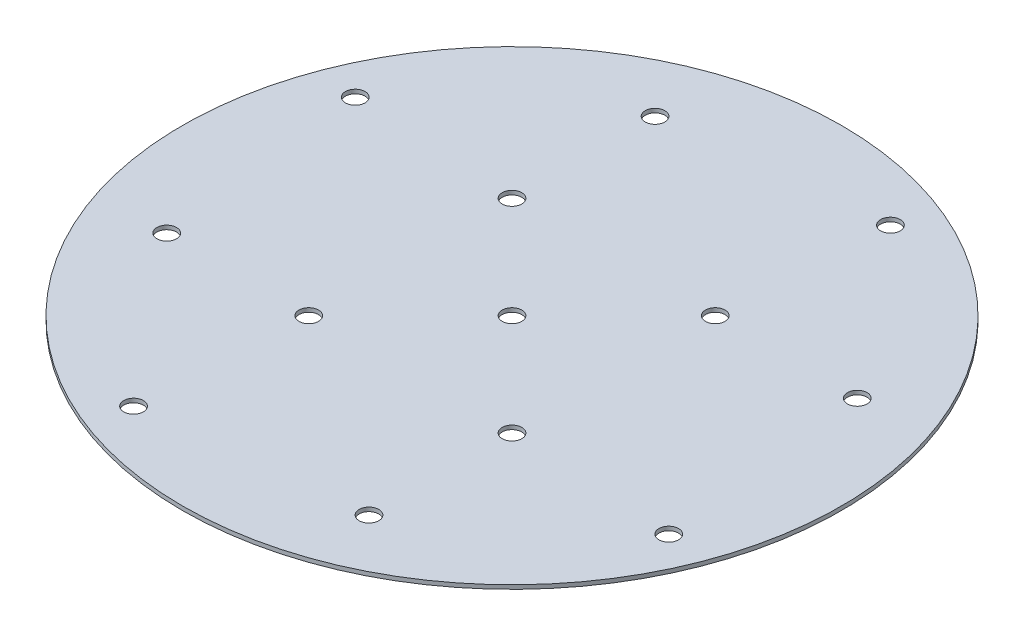
SolidWorks part; units mm, degrees
material "6061-T6 (SS)"
ref_plane "Front Plane" through (0, 0, 0) normal (0, 0, 1) x (1, 0, 0)
ref_plane "Top Plane" through (0, 0, 0) normal (0, 1, 0) x (1, 0, 0)
ref_plane "Right Plane" through (0, 0, 0) normal (1, 0, 0) x (0, 0, -1)
sketch "Sketch2" plane through (0, 0, 0) normal (1, 0, 0) x (0, 0, -1)
  line L0 (0, 0) -> (-82.55, 0)
  line L1 (-82.55, 0) -> (-82.55, 1)
  line L2 (-82.55, 1) -> (0, 1)
  line L5 (0, 1) -> (0, 0)
  dimension "D1" = 82.55
  dimension "D2" = 1
ref_axis "Axis1" through (0, -0.05, 0) along (0, 1, 0)
revolve "Revolve1" add sketch "Sketch2" angle 360 about axis through (0, -0.05, 0) along (0, 1, 0)
hole_wizard "#10 (0.1935) Diameter Hole1" positions "Sketch6" profile "Sketch7" hole size "#10" standard "ANSI Inch" end condition through all
sketch "Sketch6" plane through (0, 1, 0) normal (0, 1, 0) x (1, 0, 0)
  line L0 (0, 0) -> (-53.438, 129.0108) construction
  line L2 (0, 0) -> (0, 109.0908) construction
  line L3 (0, 0) -> (-76.2663, 31.5905) construction
  line L4 (0, 0) -> (-47.7784, 47.7784) construction
  circle A0 centre (0, 0) radius 82.55 construction
  point P0 (-25.3336, 61.1608)
  point P11 (264.7437, 73.7878)
  point P20 (-67.0275, 27.7637)
  point P22 (-25.4558, 25.4558)
  dimension "D1" = 22.5
  dimension "D2" = 66.2
  dimension "D3" = 72.55
  dimension "D4" = 45
  dimension "D6" = 22.5
  dimension "D5" = 36
sketch "Sketch7" plane through (-25.3336, 1, -61.1608) normal (1, 0, 0) x (0, 0, 1)
  line L0 (0, 0) -> (0, 1)
  line L1 (0, 1) -> (2.4574, 1)
  line L2 (2.4574, 1) -> (2.4574, 0)
  line L5 (2.4574, 0) -> (0, 0)
  line L11 (0, -6.35) -> (0, 107.95) construction
  dimension "Thru Hole Dia." = 4.9149
  dimension "Thru Hole Depth" = 1
pattern_circular "CirPattern3" count 4 over 360 about axis through (0, -0.05, 0) along (0, 1, 0) of "#10 (0.1935) Diameter Hole1"
hole_wizard "#10 (0.1935) Diameter Hole2" positions "Sketch8" profile "Sketch9" hole size "#10" standard "ANSI Inch" end condition through all
sketch "Sketch8" plane through (0, 1, 0) normal (0, 1, 0) x (1, 0, 0)
  line L0 (0, 0) -> (106.3094, -1.7118) construction
  point P7 (0, 0)
sketch "Sketch9" plane through (0, 1, 0) normal (1, 0, 0) x (0, 0, 1)
  line L0 (0, 0) -> (0, 1)
  line L1 (0, 1) -> (2.4574, 1)
  line L2 (2.4574, 1) -> (2.4574, 0)
  line L5 (2.4574, 0) -> (0, 0)
  line L11 (0, -6.35) -> (0, 107.95) construction
  dimension "Thru Hole Dia." = 4.9149
  dimension "Thru Hole Depth" = 1
equation "\"TubeDiameter\" = 6.500in"
equation "\"D1@Sketch2\"=\"TubeDiameter\"/2"
equation "\"D2@Sketch6\"=66.2"
equation "\"D3@Sketch6\"=\"TubeDiameter\"/2-10mm"
